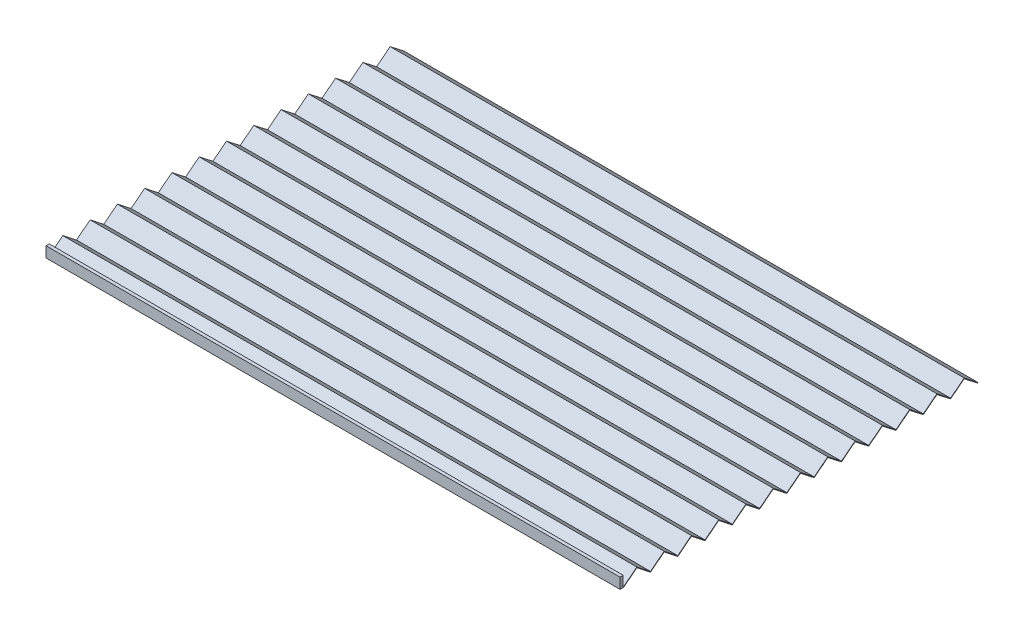
SolidWorks part; units mm, degrees
ref_plane "Front Plane" through (0, 0, 0) normal (0, 0, 1) x (1, 0, 0)
ref_plane "Top Plane" through (0, 0, 0) normal (0, 1, 0) x (1, 0, 0)
ref_plane "Right Plane" through (0, 0, 0) normal (1, 0, 0) x (0, 0, -1)
sketch "Sketch2" plane through (0, 0, 0) normal (0, 0, 1) x (1, 0, 0)
  line L1 (-270, 10) -> (270, 10)
  line L2 (-270, 10) -> (-270, 0)
  line L3 (-270, 0) -> (270, 0)
  line L4 (270, 10) -> (270, 0)
  point P4 (0, 0)
  dimension "D1" = 10
  dimension "D2" = 540
extrude "Boss-Extrude1" add sketch "Sketch2" along normal blind 3
sketch "Sketch3" plane through (270, 0, 0) normal (1, 0, 0) x (0, 0, -1)
  line L0 (0, 10) -> (333.5973, 10) construction
  line L1 (0, 0) -> (333.5973, 0) construction
  line L3 (0, 0) -> (12.8307, 10)
  line L4 (12.8307, 10) -> (25.6613, 0)
  line L5 (25.6613, 0) -> (38.492, 10)
  line L6 (38.492, 10) -> (51.3227, 0)
  line L7 (51.3227, 0) -> (64.1533, 10)
  line L8 (64.1533, 10) -> (76.984, 0)
  line L9 (76.984, 0) -> (89.8146, 10)
  line L10 (89.8146, 10) -> (102.6453, 0)
  line L11 (102.6453, 0) -> (115.476, 10)
  line L12 (115.476, 10) -> (128.3066, 0)
  line L13 (128.3066, 0) -> (141.1373, 10)
  line L14 (141.1373, 10) -> (153.968, 0)
  line L15 (153.968, 0) -> (166.7986, 10)
  line L16 (166.7986, 10) -> (179.6293, 0)
  line L17 (179.6293, 0) -> (192.46, 10)
  line L18 (192.46, 10) -> (205.2906, 0)
  line L20 (205.2906, 0) -> (218.1213, 10)
  line L21 (218.1213, 10) -> (230.9519, 0)
  line L22 (230.9519, 0) -> (243.7826, 10)
  line L23 (243.7826, 10) -> (256.6133, 0)
  line L24 (256.6133, 0) -> (269.4439, 10)
  line L25 (269.4439, 10) -> (282.2746, 0)
  line L26 (282.2746, 0) -> (295.1053, 10)
  line L27 (295.1053, 10) -> (307.9359, 0)
  line L28 (307.9359, 0) -> (320.7666, 10)
  line L29 (320.7666, 10) -> (333.5973, 0)
  line L30 (333.5973, 10) -> (333.5973, 0) construction
  line L32 (333.5973, 10) -> (333.5973, 0) construction
extrude "Extrude-Thin1" add sketch "Sketch3" against normal through all thin thin type mid plane wall 0.5
